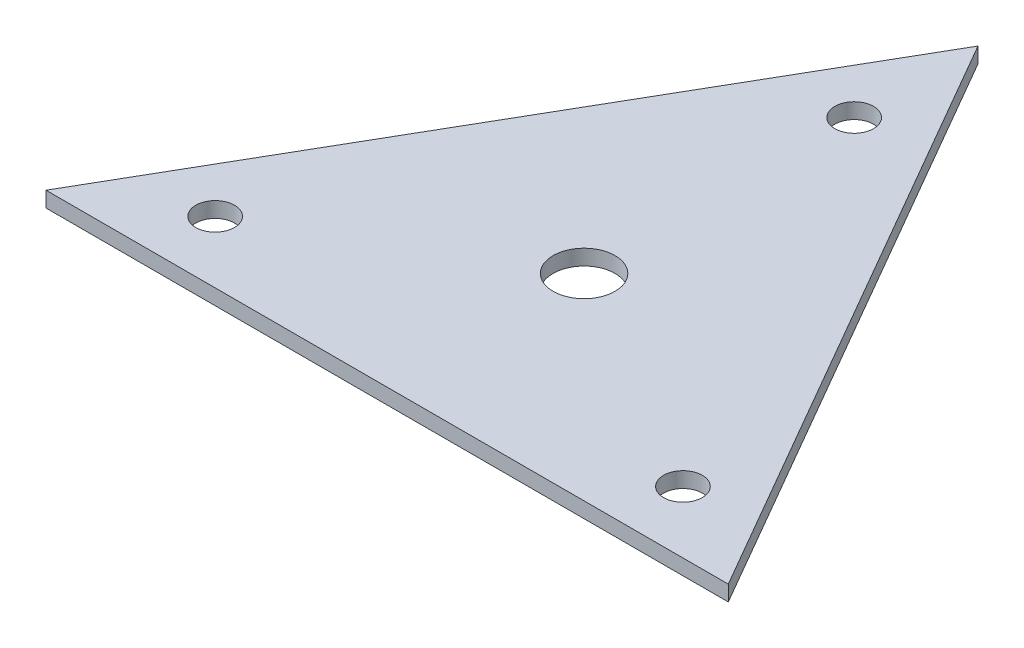
SolidWorks part; units mm, degrees
ref_plane "Front Plane" through (0, 0, 0) normal (0, 0, 1) x (1, 0, 0)
ref_plane "Top Plane" through (0, 0, 0) normal (0, 1, 0) x (1, 0, 0)
ref_plane "Right Plane" through (0, 0, 0) normal (1, 0, 0) x (0, 0, -1)
sketch "Sketch1" plane through (0, 0, 0) normal (0, 1, 0) x (1, 0, 0)
  line L0 (0, 0) -> (139.954, 0)
  line L1 (69.977, 121.2037) -> (139.954, 0)
  line L2 (69.977, 121.2037) -> (0, 0)
  line L3 (69.977, 40.4012) -> (69.977, 121.2037) construction
  line L4 (69.977, 40.4012) -> (0, 0) construction
  line L5 (69.977, 40.4012) -> (139.954, 0) construction
  circle A0 centre (69.977, 40.4012) radius 6.35
  circle A1 centre (117.957, 12.7) radius 3.9687
  circle A2 centre (21.997, 12.7) radius 3.9687
  circle A3 centre (69.977, 95.8037) radius 3.9687
  dimension "D4" = 12.7
  dimension "D5" = 30
  dimension "D7" = 7.9375
  dimension "D8" = 7.9375
  dimension "D10" = 7.9375
  dimension "D1" = 139.954
  dimension "D2" = 139.954
  dimension "D3" = 60
  dimension "D6" = 25.4
  dimension "D9" = 25.4
  dimension "D11" = 25.4
extrude "Boss-Extrude1" add sketch "Sketch1" along normal blind 3.175
sketch "Sketch2" plane through (0, 0, 0) normal (0, 1, 0) x (1, 0, 0)
  line L0 (117.957, 12.7) -> (21.997, 12.7) construction
  line L1 (21.997, 12.7) -> (69.977, 95.8037) construction
  line L2 (69.977, 95.8037) -> (117.957, 12.7) construction
  circle A0 centre (93.967, 54.2519) radius 6.35
  circle A1 centre (69.977, 12.7) radius 6.35
  circle A2 centre (45.987, 54.2519) radius 6.35
  dimension "D1" = 12.7
  dimension "D2" = 12.7
  dimension "D3" = 12.7
extrude "Cut-Extrude1" cut sketch "Sketch2" along normal blind 0.254
